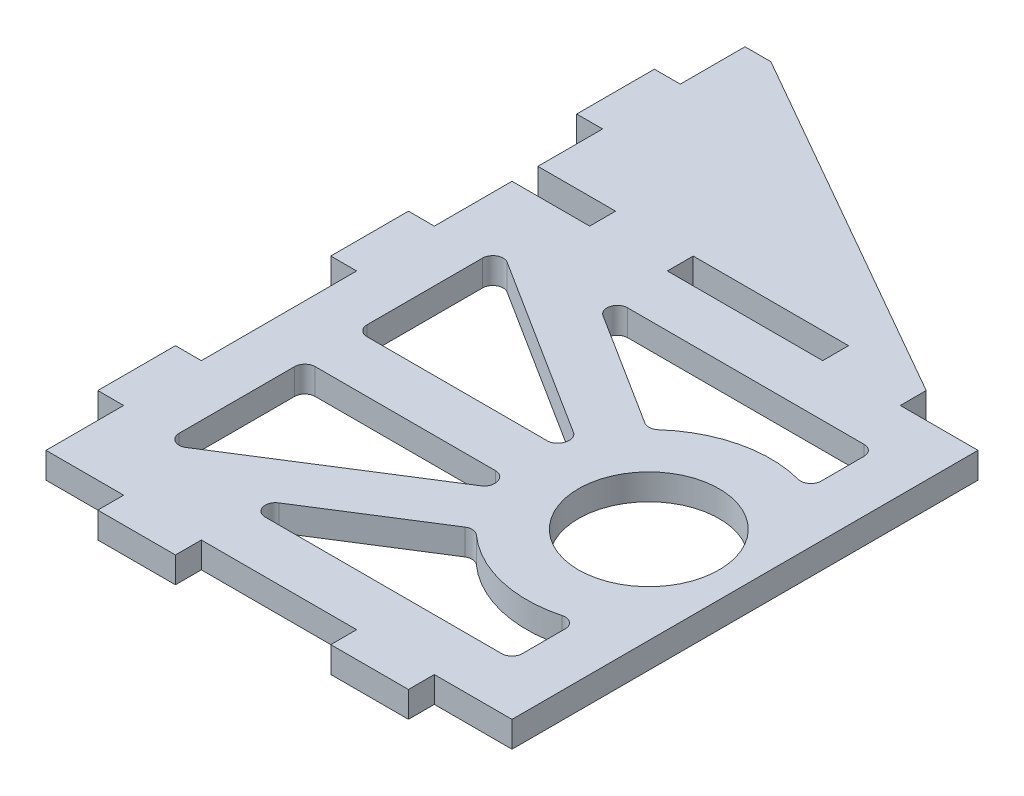
SolidWorks part; units mm, degrees
ref_plane "Front Plane" through (0, 0, 0) normal (0, 0, 1) x (1, 0, 0)
ref_plane "Top Plane" through (0, 0, 0) normal (0, 1, 0) x (1, 0, 0)
ref_plane "Right Plane" through (0, 0, 0) normal (1, 0, 0) x (0, 0, -1)
sketch "Sketch1" plane through (0, 0, 0) normal (0, 1, 0) x (1, 0, 0)
  line L0 (0, 57.15) -> (184.6638, 57.15) construction
  line L1 (0, 0) -> (19.05, 0)
  line L2 (0, 0) -> (0, 19.05)
  line L3 (0, 114.3) -> (19.05, 114.3)
  line L4 (114.3, 0) -> (114.3, 114.3)
  line L5 (38.1, 0) -> (76.2, 0)
  line L7 (95.25, 0) -> (95.25, -6.35)
  line L8 (95.25, -6.35) -> (76.2, -6.35)
  line L9 (76.2, 0) -> (76.2, -6.35)
  line L11 (19.05, 0) -> (19.05, -6.35)
  line L12 (19.05, -6.35) -> (38.1, -6.35)
  line L13 (38.1, 0) -> (38.1, -6.35)
  line L14 (95.25, 0) -> (114.3, 0)
  line L15 (38.1, 114.3) -> (38.1, 120.65)
  line L16 (19.05, 120.65) -> (38.1, 120.65)
  line L17 (19.05, 114.3) -> (19.05, 120.65)
  line L18 (76.2, 114.3) -> (76.2, 120.65)
  line L19 (95.25, 120.65) -> (76.2, 120.65)
  line L20 (95.25, 114.3) -> (95.25, 120.65)
  line L21 (38.1, 114.3) -> (76.2, 114.3)
  line L23 (95.25, 114.3) -> (114.3, 114.3)
  line L24 (-6.35, 19.05) -> (-6.35, 38.1)
  line L25 (0, 95.25) -> (-6.35, 95.25)
  line L27 (0, 76.2) -> (-6.35, 76.2)
  line L28 (-6.35, 95.25) -> (-6.35, 76.2)
  line L29 (0, 38.1) -> (-6.35, 38.1)
  line L31 (0, 19.05) -> (-6.35, 19.05)
  line L32 (0, 95.25) -> (0, 114.3)
  line L33 (0, 38.1) -> (0, 76.2)
  dimension "D1" = 114.3
  dimension "D2" = 114.3
  dimension "D3" = 19.05
  dimension "D4" = 19.05
  dimension "D5" = 19.05
  dimension "D6" = 19.05
  dimension "D7" = 6.35
  dimension "D8" = 6.35
  dimension "D9" = 19.05
  dimension "D10" = 19.05
extrude "Boss-Extrude1" add sketch "Sketch1" against normal blind 6.35
sketch "Sketch2" plane through (0, 0, 0) normal (0, 1, 0) x (1, 0, 0)
  line L0 (114.3, 57.15) -> (55.59, 57.15) construction
  line L1 (114.3, 0) -> (114.3, 114.3) construction
  line L2 (107.95, 57.15) -> (107.95, 78.6846) construction
  circle A0 centre (90.7, 57.15) radius 17.25
  dimension "D1" = 34.5001
  dimension "D2" = 6.35
extrude "Cut-Extrude1" cut sketch "Sketch2" against normal through all
sketch "Sketch3" plane through (0, 0, 0) normal (0, 1, 0) x (1, 0, 0)
  line L0 (90.7, 57.15) -> (-12.2602, 122.2732) construction
  line L1 (87.3056, 51.7834) -> (-15.6546, 116.9066)
  line L2 (94.0944, 62.5166) -> (-8.8658, 127.6398)
  line L3 (90.7, 57.15) -> (22.3264, 57.15) construction
  line L4 (90.7, 57.15) -> (-12.2602, -7.9732) construction
  line L5 (87.3056, 62.5166) -> (-15.6546, -2.6066)
  line L6 (94.0944, 51.7834) -> (-8.8658, -13.3398)
  line L35 (90.7, 57.15) -> (-12.2602, 57.15) construction
  line L36 (90.7, 50.8) -> (-12.2602, 50.8)
  line L37 (90.7, 63.5) -> (-12.2602, 63.5)
  line L63 (12.7, 12.7) -> (101.6, 12.7)
  line L64 (101.6, 12.7) -> (101.6, 101.6)
  line L65 (101.6, 101.6) -> (12.7, 101.6)
  line L66 (12.7, 101.6) -> (12.7, 12.7)
  line L67 (12.7, 12.7) -> (101.6, 12.7)
  line L68 (101.6, 12.7) -> (101.6, 101.6)
  line L69 (101.6, 101.6) -> (12.7, 101.6)
  line L70 (12.7, 101.6) -> (12.7, 12.7)
  arc A0 (87.3056, 51.7834) -> (94.0944, 62.5166) centre (90.7, 57.15) ccw
  arc A1 (-8.8658, 127.6398) -> (-15.6546, 116.9066) centre (-12.2602, 122.2732) ccw
  arc A3 (87.3056, 62.5166) -> (94.0944, 51.7834) centre (90.7, 57.15) cw
  circle A4 centre (90.7, 57.15) radius 29.95
  circle A5 centre (90.7, 57.15) radius 29.95
  arc A6 (-8.8658, -13.3398) -> (-15.6546, -2.6066) centre (-12.2602, -7.9732) cw
  arc A7 (90.7, 50.8) -> (90.7, 63.5) centre (90.7, 57.15) ccw
  arc A8 (-12.2602, 63.5) -> (-12.2602, 50.8) centre (-12.2602, 57.15) ccw
  point P2 (39.2199, 89.7116)
  point P8 (39.2199, 24.5884)
  point P19 (39.2199, 57.15)
  dimension "D2" = 6.35
  dimension "D1" = 12.7
  dimension "D3" = 12.7
extrude "Cut-Extrude2" cut sketch "Sketch3" against normal through all contours A5 L68 L69 L2 | A5 L1 L70 L37 | A5 L36 L70 L5 | A5 L6 L67 L68 region at (30.9036, 0, -75.4809) region at (30.9036, 0, -38.8191) region at (72.1425, 0, -20.8641) region at (72.1425, 0, -93.4359)
fillet "Fillet1" radius 2.54 16 edges at (61.4308, -3.175, -63.5) (12.7, -3.175, -63.5) (62.5692, -3.175, -67.4293) (101.6, -3.175, -29.2539) (101.6, -3.175, -12.7) (32.3033, -3.175, -12.7) (69.3581, -3.175, -36.1375) (69.3581, -3.175, -78.1625) (32.3033, -3.175, -101.6) (101.6, -3.175, -101.6) (101.6, -3.175, -85.0461) (62.5692, -3.175, -46.8707) (12.7, -3.175, -15.328) (12.7, -3.175, -50.8) (61.4308, -3.175, -50.8) (12.7, -3.175, -98.972)
sketch "Sketch4" plane through (0, 0, 0) normal (0, 1, 0) x (1, 0, 0)
  line L0 (0, 171.45) -> (6.35, 171.45)
  line L1 (6.35, 171.45) -> (95.25, 120.65)
  line L2 (95.25, 120.65) -> (76.2, 120.65) construction
  line L3 (0, 120.65) -> (0, 136.525)
  line L4 (0, 114.3) -> (0, 95.25) construction
  line L9 (19.05, 114.3) -> (0, 114.3) construction
  line L10 (0, 155.575) -> (0, 171.45)
  line L11 (95.25, 114.3) -> (95.25, 120.65) construction
  line L12 (0, 120.65) -> (19.05, 120.65)
  line L13 (-6.35, 155.575) -> (-6.35, 136.525)
  line L14 (-6.35, 136.525) -> (0, 136.525)
  line L16 (0, 155.575) -> (-6.35, 155.575)
  line L17 (19.05, 120.65) -> (95.25, 120.65)
  dimension "D1" = 6.35
  dimension "D2" = 22.225
  dimension "D3" = 6.35
  dimension "D4" = 19.05
  dimension "D5" = 15.875
extrude "Boss-Extrude2" add sketch "Sketch4" against normal blind 6.35
